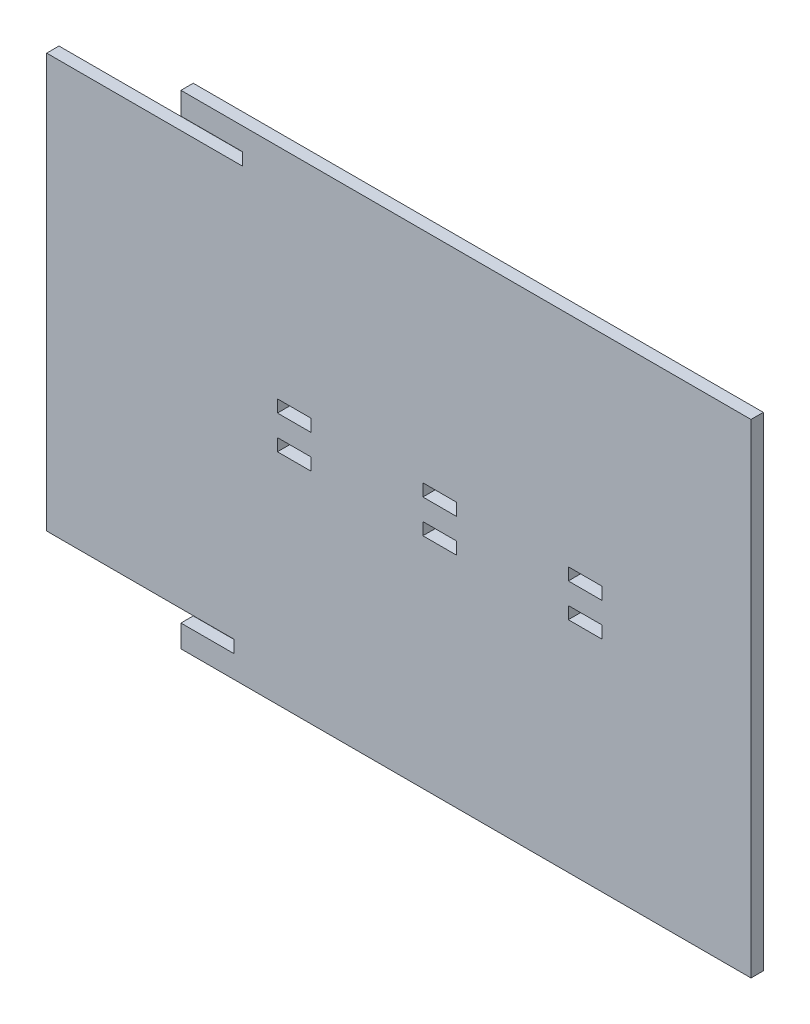
SolidWorks part; units mm, degrees
ref_plane "Alzado" through (0, 0, 0) normal (0, 0, 1) x (1, 0, 0)
ref_plane "Planta" through (0, 0, 0) normal (0, 1, 0) x (1, 0, 0)
ref_plane "Vista lateral" through (0, 0, 0) normal (1, 0, 0) x (0, 0, -1)
sketch "Croquis1" plane through (0, 0, 0) normal (0, 0, 1) x (1, 0, 0)
  line L0 (27.3312, -0.2) -> (27.3312, -216.4)
  line L1 (27.3312, -216.4) -> (-227.4739, -216.4)
  line L2 (-227.4739, -216.4) -> (-227.4739, -206.4)
  line L3 (-227.4739, -206.4) -> (-203.8311, -206.4)
  line L5 (-203.8311, -200.8) -> (-287.4739, -200.8)
  line L6 (-287.4739, -200.8) -> (-287.4739, -15.8)
  line L7 (-287.4739, -15.8) -> (-200, -15.8)
  line L8 (-200, -15.8) -> (-200, -10.2)
  line L9 (-200, -10.2) -> (-227.4739, -10.2)
  line L10 (-227.4739, -10.2) -> (-227.4739, -0.2)
  line L11 (-227.4739, -0.2) -> (27.3312, -0.2)
  line L12 (27.3312, -201) -> (27.3312, -16) construction
  line L14 (-203.8311, -206.4) -> (-203.8311, -200.8)
  line L16 (-238.318, -200.8) -> (-269.0059, -200.8) construction
  dimension "D1" = 185
  dimension "D2" = 5.6
  dimension "D3" = 5.6
  dimension "D4" = 60
  dimension "D5" = 10
  dimension "D9" = 216.2
  dimension "D10" = 196.2
  dimension "D11" = 60
extrude "Saliente-Extruir1" add sketch "Croquis1" along normal blind 5.5
sketch "Croquis2" plane through (0, 0, 5.5) normal (0, 0, 1) x (1, 0, 0)
  line L0 (-287.4739, -108.3) -> (79.9954, -108.3) construction
  line L5 (-287.4739, -15.8) -> (-287.4739, -200.8) construction
  line L6 (-54.337, -113.05) -> (-39.337, -113.05)
  line L7 (-119.337, -98.05) -> (-104.337, -98.05)
  line L8 (-184.337, -98.05) -> (-169.337, -98.05)
  line L9 (-184.337, -98.05) -> (-184.337, -103.55)
  line L10 (-184.337, -103.55) -> (-169.337, -103.55)
  line L11 (-169.337, -98.05) -> (-169.337, -103.55)
  line L28 (-119.337, -98.05) -> (-119.337, -103.55)
  line L29 (-119.337, -103.55) -> (-104.337, -103.55)
  line L30 (-104.337, -98.05) -> (-104.337, -103.55)
  line L31 (-54.337, -98.05) -> (-39.337, -98.05)
  line L32 (-54.337, -98.05) -> (-54.337, -103.55)
  line L33 (-54.337, -103.55) -> (-39.337, -103.55)
  line L34 (-39.337, -98.05) -> (-39.337, -103.55)
  line L35 (-39.337, -118.55) -> (-39.337, -113.05)
  line L36 (-54.337, -118.55) -> (-39.337, -118.55)
  line L37 (-54.337, -118.55) -> (-54.337, -113.05)
  line L38 (-104.337, -118.55) -> (-104.337, -113.05)
  line L39 (-119.337, -118.55) -> (-104.337, -118.55)
  line L40 (-119.337, -118.55) -> (-119.337, -113.05)
  line L41 (-119.337, -113.05) -> (-104.337, -113.05)
  line L42 (-184.337, -118.55) -> (-184.337, -113.05)
  line L43 (-184.337, -118.55) -> (-169.337, -118.55)
  line L44 (-169.337, -118.55) -> (-169.337, -113.05)
  line L45 (-184.337, -113.05) -> (-169.337, -113.05)
  dimension "D1" = 4.75
  dimension "D2" = 5.5
  dimension "D3" = 15
  dimension "D4" = 50
  dimension "D5" = 50
  dimension "D6" = 15
  dimension "D7" = 15
extrude "Cortar-Extruir2" cut sketch "Croquis2" against normal blind 5.5 contours L34 L31 L32 L33 | L37 L36 L35 L6 | L30 L7 L28 L29 | L41 L40 L39 L38 | L45 L42 L43 L44 | L11 L8 L9 L10 region at (-46.837, -115.8, 5.5) region at (-111.837, -100.8, 5.5) region at (-176.837, -100.8, 5.5) region at (-46.837, -100.8, 5.5) region at (-111.837, -115.8, 5.5) region at (-176.837, -115.8, 5.5)
